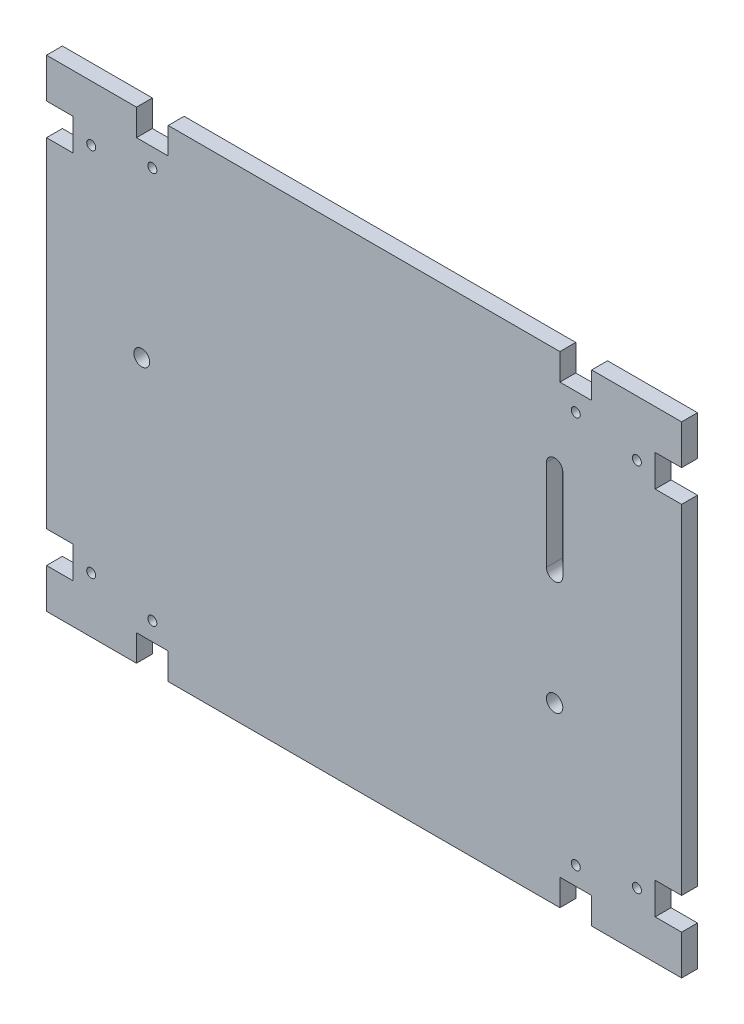
SolidWorks part; units mm, degrees
ref_plane "Front Plane" through (0, 0, 0) normal (0, 0, 1) x (1, 0, 0)
ref_plane "Top Plane" through (0, 0, 0) normal (0, 1, 0) x (1, 0, 0)
ref_plane "Right Plane" through (0, 0, 0) normal (1, 0, 0) x (0, 0, -1)
sketch "Sketch1" plane through (0, 0, 0) normal (0, 0, 1) x (1, 0, 0)
  line L1 (0, 0) -> (120, 0)
  line L2 (0, 0) -> (0, -91)
  line L3 (0, -91) -> (120, -91)
  line L4 (120, 0) -> (120, -91)
  dimension "D6" = 120
  dimension "D7" = 91
extrude "Boss-Extrude1" add sketch "Sketch1" along normal blind 3 contours L2 L3 L4 L1 region at (60, -45.5, 0)
sketch "Sketch3" plane through (0, 0, 3) normal (0, 0, 1) x (1, 0, 0)
  line L0 (96, -28) -> (96, -58)
  line L3 (17.9908, -42) -> (18.0092, -42) construction
  line L4 (0, 0) -> (0, -91) construction
  line L6 (96, -19.4399) -> (96, -36.5601) construction
  line L7 (97.55, -19.4399) -> (97.55, -36.5601)
  line L8 (0, -40.5) -> (120, -40.5) construction
  line L9 (94.45, -19.4399) -> (94.45, -36.5601)
  line L10 (58.5, -32.5) -> (69, -32.5) construction
  line L11 (0, 0) -> (120, 0) construction
  circle A0 centre (18, -40.5) radius 1.5
  circle A7 centre (96, -58) radius 1.55
  arc A8 (97.55, -19.4399) -> (94.45, -19.4399) centre (96, -19.4399) ccw
  arc A9 (94.45, -36.5601) -> (97.55, -36.5601) centre (96, -36.5601) ccw
  circle A10 centre (58.5, -32.5) radius 1.25
  circle A11 centre (69, -32.5) radius 1.25
  point P5 (95.0858, -40.5)
  point P6 (80.8564, -48.2507)
  point P11 (80.8564, -26.3273)
  point P12 (96, -28)
  point P26 (74.8579, -42)
  dimension "D1" = 3
  dimension "D2" = 30
  dimension "D3" = 18
  dimension "D4" = 78
  dimension "D5" = 3.1
  dimension "D8" = 2.5
  dimension "D7" = 27
  dimension "D6" = 17.5
  dimension "D9" = 10.5
  dimension "D10" = 8
  dimension "D11" = 40.5
extrude "Cut-Extrude1" cut sketch "Sketch3" against normal up to surface (3 mm away) contours A8 L9 A9 L7 | A0 | A7 up to face at (60, -45.5, 0)
sketch "Sketch10" plane through (0, 0, 3) normal (0, 0, 1) x (1, 0, 0)
  line L0 (0, -10.5) -> (8.45, -10.5) construction
  line L1 (0, -7.5) -> (5, -7.5)
  line L2 (0, -7.5) -> (0, -13.5)
  line L3 (0, -13.5) -> (5, -13.5)
  line L4 (5, -7.5) -> (5, -13.5)
  line L5 (60, 0) -> (60, -91) construction
  line L6 (0, 0) -> (120, 0) construction
  line L7 (0, -91) -> (120, -91) construction
  line L8 (0, -45.5) -> (120, -45.5) construction
  line L9 (0, 0) -> (0, -91) construction
  line L10 (120, 0) -> (120, -91) construction
  line L11 (0, -80.5) -> (8.45, -80.5) construction
  line L12 (5, -83.5) -> (5, -77.5)
  line L13 (0, -77.5) -> (5, -77.5)
  line L14 (0, -83.5) -> (0, -77.5)
  line L15 (0, -83.5) -> (5, -83.5)
  line L16 (120, -10.5) -> (111.55, -10.5) construction
  line L17 (115, -7.5) -> (115, -13.5)
  line L18 (120, -13.5) -> (115, -13.5)
  line L19 (120, -7.5) -> (120, -13.5)
  line L20 (120, -7.5) -> (115, -7.5)
  line L21 (120, -80.5) -> (111.55, -80.5) construction
  line L22 (120, -83.5) -> (115, -83.5)
  line L23 (120, -83.5) -> (120, -77.5)
  line L24 (120, -77.5) -> (115, -77.5)
  line L25 (115, -83.5) -> (115, -77.5)
  line L26 (20, -8.45) -> (20, 0) construction
  line L27 (17, 0) -> (17, -5)
  line L32 (17, 0) -> (23, 0)
  line L33 (17, 0) -> (17, -5)
  line L38 (17, -5) -> (23, -5)
  line L39 (23, 0) -> (23, -5)
  line L40 (23, 0) -> (23, -5)
  line L41 (0, -7.5) -> (5, -7.5)
  line L42 (0, -13.5) -> (5, -13.5)
  line L43 (17, 0) -> (17, -5)
  line L44 (17, 0) -> (17, -5)
  line L45 (23, 0) -> (23, -5)
  line L46 (23, 0) -> (23, -5)
  line L47 (100, -8.45) -> (100, 0) construction
  line L48 (97, 0) -> (97, -5)
  line L49 (97, 0) -> (97, -5)
  line L50 (103, 0) -> (103, -5)
  line L51 (103, 0) -> (103, -5)
  line L52 (97, 0) -> (97, -5)
  line L53 (97, 0) -> (97, -5)
  line L54 (103, -5) -> (97, -5)
  line L55 (103, 0) -> (103, -5)
  line L56 (103, 0) -> (97, 0)
  line L57 (103, 0) -> (103, -5)
  line L58 (100, -82.55) -> (100, -91) construction
  line L59 (103, -91) -> (103, -86)
  line L60 (103, -91) -> (97, -91)
  line L61 (103, -91) -> (103, -86)
  line L62 (103, -86) -> (97, -86)
  line L63 (97, -91) -> (97, -86)
  line L64 (97, -91) -> (97, -86)
  line L65 (103, -91) -> (103, -86)
  line L66 (103, -91) -> (103, -86)
  line L67 (97, -91) -> (97, -86)
  line L68 (97, -91) -> (97, -86)
  line L69 (20, -82.55) -> (20, -91) construction
  line L70 (23, -91) -> (23, -86)
  line L71 (23, -91) -> (23, -86)
  line L72 (17, -91) -> (17, -86)
  line L73 (17, -91) -> (17, -86)
  line L74 (23, -91) -> (23, -86)
  line L75 (23, -91) -> (23, -86)
  line L76 (17, -86) -> (23, -86)
  line L77 (17, -91) -> (17, -86)
  line L78 (17, -91) -> (23, -91)
  line L79 (17, -91) -> (17, -86)
  circle A0 centre (8.45, -10.5) radius 0.85
  circle A1 centre (8.45, -80.5) radius 0.85
  circle A2 centre (111.55, -10.5) radius 0.85
  circle A3 centre (111.55, -80.5) radius 0.85
  circle A8 centre (20, -8.45) radius 0.85
  circle A9 centre (100, -8.45) radius 0.85
  circle A10 centre (100, -82.55) radius 0.85
  circle A11 centre (20, -82.55) radius 0.85
  line M11 (120, -91) -> (120, 0)
  line M12 (120, 0) -> (0, 0)
  line M13 (0, 0) -> (0, -91)
  line M14 (0, -91) -> (120, -91)
  dimension "D3" = 1.7
  dimension "D9" = 1.7
  dimension "D1" = 6
  dimension "D2" = 5
  dimension "D4" = 8.45
  dimension "D5" = 6
  dimension "D6" = 70
  dimension "D7" = 5
  dimension "D8" = 80
  dimension "D10" = 8.45
  dimension "D11" = 10.5
extrude "Cut-Extrude5" cut sketch "Sketch10" against normal through all contours L4 L1 L3 M13 | A0 | A8 | L39 L27 L38 M12 | L15 L12 L13 M13 | A1 | L54 L50 L48 M12 | A9 | A2 | L20 L17 L18 M11 | L25 L22 L24 M11 | A3 | L76 L72 L70 M14 | L63 L59 L62 M14 | A10 | A11 region at (2.5, -10.5, 3) region at (2.5, -80.5, 3) region at (20, -2.5, 3) region at (100, -2.5, 3) region at (20, -88.5, 3) region at (100, -88.5, 3) region at (117.5, -10.5, 3) region at (117.5, -80.5, 3) region at (8.45, -10.5, 3) region at (8.45, -80.5, 3) region at (111.55, -10.5, 3) region at (111.55, -80.5, 3) region at (20, -8.45, 3) region at (100, -8.45, 3) region at (100, -82.55, 3)
sketch "Sketch8" plane through (0, 0, 0) normal (-1, 0, 0) x (0, 0, 1)
  line L0 (0, -3.75) -> (3, -3.75) construction
  line L1 (0, 0) -> (0, -7.5) construction
  line L2 (3, 0) -> (3, -7.5) construction
  line L3 (1.5, 31.25) -> (1.5, -38.75)
  circle A0 centre (1.5, -38.75) radius 0.85
  circle A1 centre (1.5, 31.25) radius 0.85
  point P9 (1.5, -3.75)
  dimension "D2" = 1.7
  dimension "D1" = 70
extrude "Cut-Extrude4" cut sketch "Sketch8" against normal blind 10 contours A0 | A1
